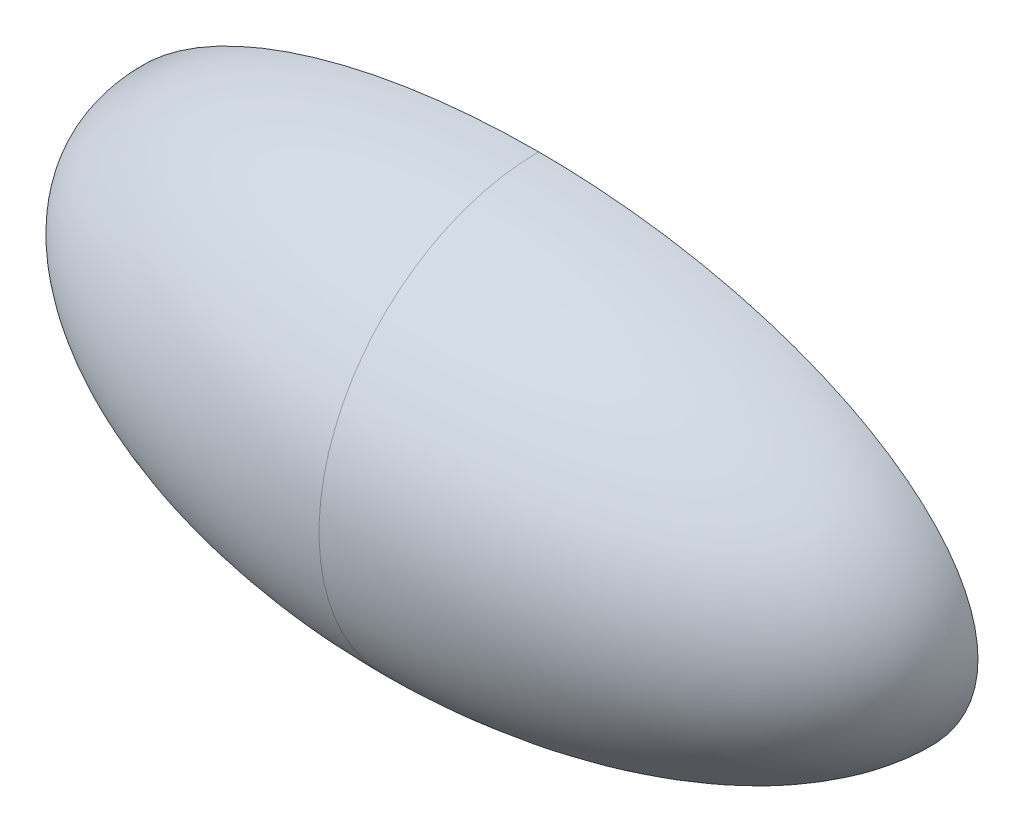
SolidWorks part; units mm, degrees
ref_plane "Front Plane" through (0, 0, 0) normal (0, 0, 1) x (1, 0, 0)
ref_plane "Top Plane" through (0, 0, 0) normal (0, 1, 0) x (1, 0, 0)
ref_plane "Right Plane" through (0, 0, 0) normal (1, 0, 0) x (0, 0, -1)
sketch "Sketch1" plane through (0, 0, 0) normal (0, 0, 1) x (1, 0, 0)
  line L0 (0, 0) -> (12, 0) construction
  line L1 (0, 0) -> (0, 6) construction
  line L2 (0, 0) -> (-12.0496, 0) construction
  line L3 (-12.0496, 0) -> (12, 0)
  ellipse E0 centre (0, 0) end of major axis (12, 0) minor radius 6 (0, 6) -> (12, 0) cw
  ellipse E1 centre (0, 0) end of major axis (-12.0496, 0) minor radius 6 (0, 6) -> (-12.0496, 0) ccw
  dimension "D1" = 6
  dimension "D2" = 12
revolve "Revolve1" add sketch "Sketch1" angle 180 about L3
